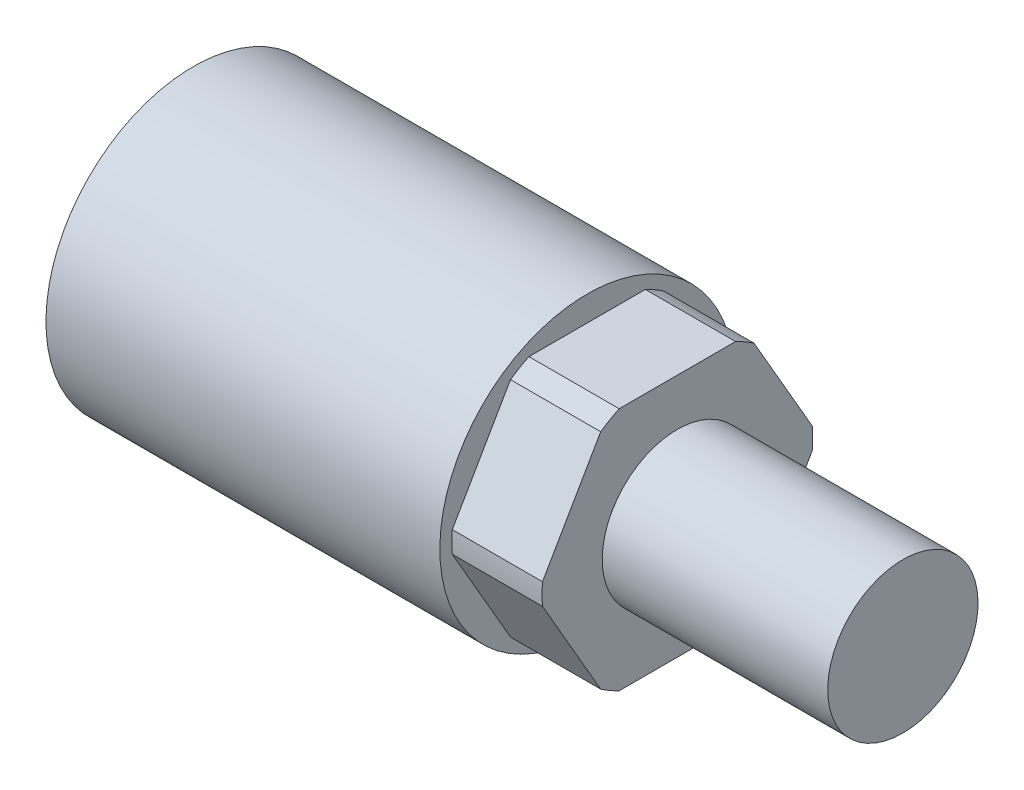
SolidWorks part; units mm, degrees
ref_plane "XY" through (0, 0, 0) normal (0, 0, 1) x (1, 0, 0)
ref_plane "XZ" through (0, 0, 0) normal (0, 1, 0) x (1, 0, 0)
ref_plane "YZ" through (0, 0, 0) normal (1, 0, 0) x (0, 0, -1)
ref_axis "X" through (-88.99, 0, 0) along (1, 0, 0)
ref_axis "Y" through (0, -55, 0) along (0, 1, 0)
ref_axis "Z" through (0, 0, 55) along (0, 0, -1)
sketch "Sketch1" plane through (0, 0, 0) normal (0, 0, 1) x (1, 0, 0)
  line L0 (0, 0) -> (0, 6.35) construction
  line L1 (0, 11.43) -> (-7.62, 11.43)
  line L2 (-7.62, 11.43) -> (-7.62, 12.446)
  line L3 (-7.62, 12.446) -> (-40.894, 12.446)
  line L4 (-40.894, 12.446) -> (-40.894, 0)
  line L5 (-40.894, 0) -> (19.05, 0)
  line L6 (19.05, 0) -> (19.05, 6.35)
  line L7 (19.05, 6.35) -> (0, 6.35)
  line L8 (0, 6.35) -> (0, 11.43)
  dimension "D1" = 40.894
  dimension "D2" = 6.35
  dimension "D3" = 12.446
  dimension "D4" = 11.43
  dimension "D5" = 7.62
  dimension "D6" = 19.05
revolve "Revolve1" add sketch "Sketch1" angle 360 about L5
sketch "Sketch3" plane through (0, 0, 0) normal (1, 0, 0) x (0, 0, -1)
  line L1 (5.9575, 10.3188) -> (-5.9575, 10.3188)
  line L2 (-5.9575, 10.3188) -> (-11.9151, 0)
  line L3 (-11.9151, 0) -> (-5.9575, -10.3188)
  line L4 (-5.9575, -10.3188) -> (5.9575, -10.3188)
  line L5 (5.9575, -10.3188) -> (11.9151, 0)
  line L6 (11.9151, 0) -> (5.9575, 10.3188)
  circle A0 centre (0, 0) radius 10.3188 construction
  dimension "D1" = 20.6375
extrude "Cut-Extrude5" cut sketch "Sketch3" against normal up to surface (7.62 mm away) flip side to cut up to face at (-7.62, -12.446, 0)
